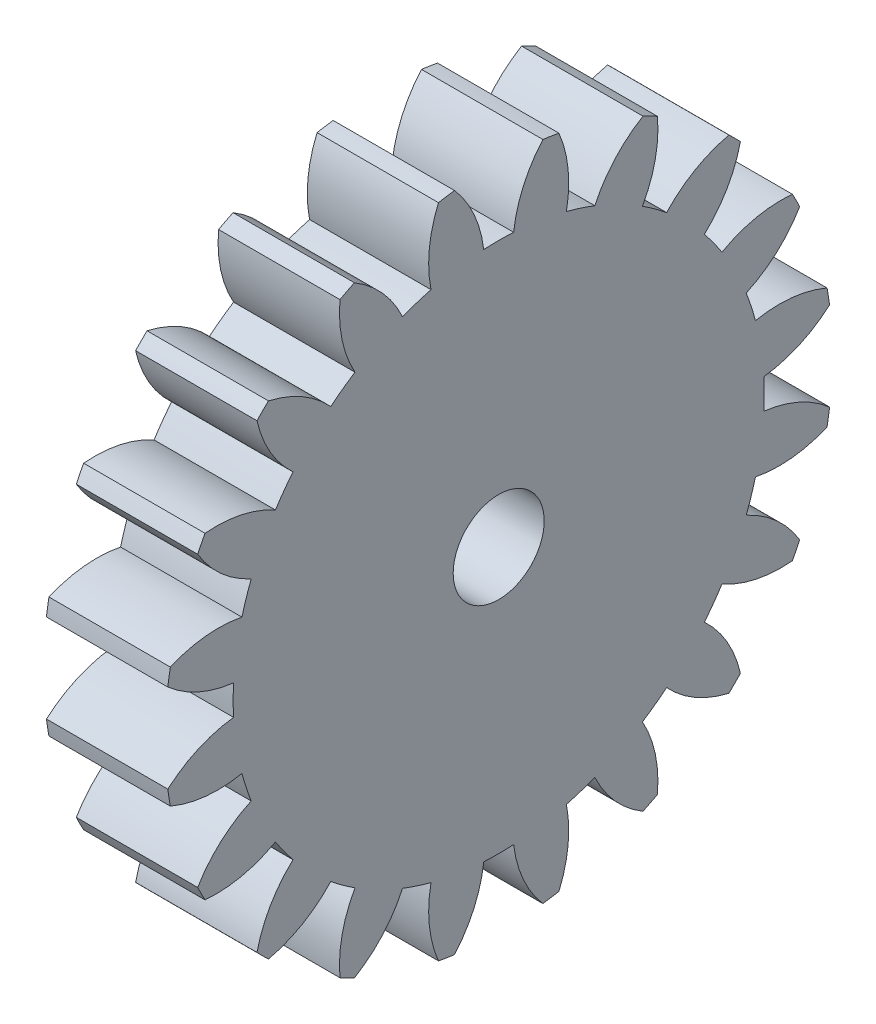
SolidWorks part; units mm, degrees
ref_plane "Plane1" through (0, 0, 0) normal (0, 0, 1) x (1, 0, 0)
ref_plane "Plane2" through (0, 0, 0) normal (0, 1, 0) x (1, 0, 0)
ref_plane "Plane3" through (0, 0, 0) normal (1, 0, 0) x (0, 0, -1)
sketch "HoldingSke" plane through (0, 0, 0) normal (0, 1, 0) x (1, 0, 0)
  line L0 (0, 0) -> (0.1879, -0.0684)
  line L1 (-15, 0) -> (100, 0) construction
  line L2 (0, 0) -> (-2.1039, 2.3779)
  line L3 (0, 0) -> (-11.863, 4.5341)
  line L4 (0, 0) -> (8.1152, 2.9537)
  line L5 (0, 0) -> (-46.8476, -17.4728)
  line L6 (0, 0) -> (-16.5793, -11.1861)
  line L7 (-2.1039, 2.3779) -> (8.6586, 51.2059)
  line L8 (-76.2, 54.61) -> (-73.9, 54.61)
  line L9 (-71.009, 38.7566) -> (-53.1078, 45.2721)
  line L10 (-76.2, 71.12) -> (104.1128, 71.12)
  line L11 (0, 0) -> (-20, 0)
  line L12 (-76.2, 101.6) -> (-76.033, 101.6)
  line L13 (24.9733, 27.94) -> (52.9518, 28.4284)
  line L14 (24.9733, 27.94) -> (24.9743, 27.94)
  line L15 (24.9733, 27.94) -> (100.4006, 29.5858)
  line L16 (-63.627, -5) -> (-12.827, -5)
  circle A0 centre (0, 0) radius 7.5
  circle A1 centre (0, 0) radius 37.5
  circle A2 centre (0, 0) radius 37.5
  circle A3 centre (0, 0) radius 7.5
  dimension "MHD" = 75
  dimension "Hub_dia" = 75
  dimension "Bore" = 15
  dimension "MBD" = 15
  dimension "Num_teeth" = 20
  dimension "Pitch_radius" = 180.3128
  dimension "Pitch" = 0.2
  dimension "Width" = 20
  dimension "Overall_len" = 50
  dimension "Show_teeth" = 20
  dimension "Thickness" = 20
  dimension "OAL" = 50.0001
  dimension "T_dim" = 2.3
  dimension "Ap" = 20
  dimension "H" = 19.05
  dimension "Backlash" = 0.167
  dimension "Addendum_fac" = 1
  dimension "Dedendum_fac" = 1.25
  dimension "Clearance_fac" = 0.25
  dimension "Dedendum_add" = 0.001
  dimension "Module" = 5
sketch "BasProSke" plane through (0, 0, 0) normal (0, 1, 0) x (1, 0, 0)
  line L0 (-10, 0) -> (60, 0) construction
  line L1 (0, 0) -> (0, 55)
  line L2 (0, 0) -> (20, 0)
  line L3 (20, 0) -> (20, 55)
  line L4 (20, 55) -> (0, 55)
  dimension "Diameter" = 110
  dimension "Thickness" = 20
revolve "Base-Revolve" add sketch "BasProSke" angle 360 about L0
sketch "TooCutSke" plane through (0, 0, 0) normal (1, 0, 0) x (0, 0, -1)
  line L1 (0, 0) -> (0, 107) construction
  line L2 (0, 0) -> (-4.2151, 49.822) construction
  line L3 (0, 0) -> (-15.6021, 98.5081) construction
  line L4 (-4.2151, 49.822) -> (-7.8011, 49.254) construction
  arc A0 (2.4648, 43.6795) -> (-2.4648, 43.6795) centre (0, 0) ccw
  arc A1 (7.3009, 54.5389) -> (-7.3009, 54.5389) centre (0, 0) ccw
  circle A2 centre (0, 0) radius 50 construction
  circle A3 centre (0, 0) radius 46.9846 construction
  arc A4 (-2.4648, 43.6795) -> (-7.3009, 54.5389) centre (-22.3276, 41.3405) ccw
  arc A5 (7.3009, 54.5389) -> (2.4648, 43.6795) centre (22.3276, 41.3405) ccw
  dimension "Root_dia" = 87.498
  dimension "Overcut_dia" = 110.0508
  dimension "Pitch_dia" = 100
  dimension "Base_dia" = 93.9693
  dimension "Flank_rad" = 20
  dimension "Half_ang" = 9
  dimension "Half_CT" = 3.6307
extrude "ToothCut" cut sketch "TooCutSke" along normal through all
fillet "Breaks" [suppressed] radius 0.1 tangent propagation no
fillet "RootFillets" [suppressed] radius 1.251
pattern_circular "TeethCuts" count 20 every 18 about axis through (-10, 0, 0) along (1, 0, 0) of "ToothCut", "RootFillets", "Breaks"
sketch "HubNeaOneSke" [suppressed] plane through (0, 0, 0) normal (-1, 0, 0) x (0, 0, 1)
  circle A0 centre (0, 0) radius 12.7
  dimension "Diameter" = 75
extrude "HubNearOne" [suppressed] add sketch "HubNeaOneSke" along normal blind 30.0001
sketch "HubNeaBotSke" [suppressed] plane through (0, 0, 0) normal (-1, 0, 0) x (0, 0, 1)
  circle A0 centre (0, 0) radius 12.7
  dimension "Diameter" = 75
extrude "HubNearBoth" [suppressed] add sketch "HubNeaBotSke" along normal blind 15
ref_plane "FarPln" through (20, 0, 0) normal (1, 0, 0) x (0, 0, -1)
sketch "HubFarSke" [suppressed] plane through (12.7, 0, 0) normal (1, 0, 0) x (0, 0, -1)
  circle A0 centre (0, 0) radius 12.7
  dimension "Diameter" = 75
extrude "HubFar" [suppressed] add sketch "HubFarSke" along normal blind 15
sketch "BorSke" plane through (0, 0, 0) normal (1, 0, 0) x (0, 0, -1)
  circle A0 centre (0, 0) radius 7.5
  dimension "Diameter" = 15
extrude "Bore" cut sketch "BorSke" along normal mid plane 100.0001
sketch "KeySke" [suppressed] plane through (0, 0, 0) normal (1, 0, 0) x (0, 0, -1)
  line L0 (-3.175, 0) -> (-3.175, 12.065)
  line L1 (-3.175, 12.065) -> (3.175, 12.065)
  line L2 (3.175, 12.065) -> (3.175, 0)
  line L3 (0, 0) -> (0, 34) construction
  line L4 (-3.175, 0) -> (3.175, 0)
  dimension "Offset" = 9.8
  dimension "Width" = 5
extrude "Keyway" [suppressed] cut sketch "KeySke" along normal mid plane 100.0001
pattern_circular "Keyway2" [suppressed] count 2 every 90 about axis through (-10, 0, 0) along (1, 0, 0)
ref_axis "Axis1" through (20, 0, 0) along (-1, 0, 0)
equation "' \"Module@HoldingSke\" = 6.35"
equation "' \"Num_teeth@HoldingSke\" = 12"
equation "' \"Ap@HoldingSke\" =  20"
equation "' \"Width@HoldingSke\" = 0.5 * 25.4"
equation "' \"Hub_dia@HoldingSke\"= 1 * 25.4"
equation "' \"Overall_len@HoldingSke\" = 1.0 * 25.4"
equation "' \"Bore@HoldingSke\" = 0.75 * 25.4"
equation "' \"T_dim@HoldingSke\" = 0.1 * 25.4"
equation "' \"Width@KeySke\" = 0.25 * 25.4"
equation "' \"Show_teeth@HoldingSke\" = 13"
equation "' \"Backlash@HoldingSke\" = 0.009 * 25.4"
equation "' \"Addendum_fac@HoldingSke\" = 1.0"
equation "' \"Dedendum_fac@HoldingSke\" = 1.25"
equation "' \"Dedendum_add@HoldingSke\" = 0.00005 * 25.4"
equation "' \"Clearance_fac@HoldingSke\" = 0.25"
equation "\"Pitch@HoldingSke\" = 1 / \"Module@HoldingSke\""
equation "\"Overcut_dia@TooCutSke\" = (\"Num_teeth@HoldingSke\" + 2 * \"Addendum_fac@HoldingSke\") / \"Pitch@HoldingSke\" + 0.002 * 25.4"
equation "\"Pitch_dia@TooCutSke\" = \"Num_teeth@HoldingSke\" / \"Pitch@HoldingSke\""
equation "\"Base_dia@TooCutSke\" = \"Num_teeth@HoldingSke\" / \"Pitch@HoldingSke\" * cos((\"Ap@HoldingSke\"  * 3.14159265 / 180))"
equation "\"Root_dia@TooCutSke\" = (\"Num_teeth@HoldingSke\" + 2) / \"Pitch@HoldingSke\" - 2 * (\"Addendum_fac@HoldingSke\" + \"Dedendum_fac@HoldingSke\") / \"Pitch@HoldingSke\" - \"Dedendum_add@HoldingSke\" * 2"
equation "\"Half_ang@TooCutSke\" = 180 / \"Num_teeth@HoldingSke\""
equation "\"Half_CT@TooCutSke\" = \"Num_teeth@HoldingSke\" / \"Pitch@HoldingSke\" * sin((3.14159265 / 2 / \"Num_teeth@HoldingSke\")) / 2 - 7 * \"Backlash@HoldingSke\" / 4"
equation "\"Flank_rad@TooCutSke\" = \"Num_teeth@HoldingSke\" / \"Pitch@HoldingSke\" / 5"
equation "\"Radius@RootFillets\" = \"Clearance_fac@HoldingSke\" / \"Pitch@HoldingSke\" + \"Dedendum_add@HoldingSke\""
equation "\"Break_rad@Breaks\" = 0.02 / \"Pitch@HoldingSke\""
equation "\"Thickness@HoldingSke\" = \"Width@HoldingSke\""
equation "\"OAL@HoldingSke\" = \"Thickness@HoldingSke\""
equation "\"MHD@HoldingSke\" = (\"Num_teeth@HoldingSke\" + 2) / \"Pitch@HoldingSke\" - 2 * (\"Addendum_fac@HoldingSke\" + \"Dedendum_fac@HoldingSke\")  / \"Pitch@HoldingSke\" - \"Dedendum_add@HoldingSke\" * 2"
equation "\"MBD@HoldingSke\" = (\"Num_teeth@HoldingSke\" + 2) / \"Pitch@HoldingSke\" - 2 * (\"Addendum_fac@HoldingSke\" + \"Dedendum_fac@HoldingSke\")  / \"Pitch@HoldingSke\" - \"Dedendum_add@HoldingSke\" * 2 - 0.002 * 25.4"
equation "\"MHD@HoldingSke\" = ((sgn( \"MHD@HoldingSke\" - \"Hub_dia@HoldingSke\" )-1)*( \"MHD@HoldingSke\" - \"Hub_dia@HoldingSke\" ))/-2+ \"Hub_dia@HoldingSke\""
equation "\"MBD@HoldingSke\" = ((sgn( \"MBD@HoldingSke\" - \"Bore@HoldingSke\" )-1)*( \"MBD@HoldingSke\" - \"Bore@HoldingSke\" ))/-2+ \"Bore@HoldingSke\""
equation "\"OAL@HoldingSke\" = ((sgn( \"OAL@HoldingSke\" - \"Overall_len@HoldingSke\" )+1)*( \"OAL@HoldingSke\" - \"Overall_len@HoldingSke\" ))/2 + \"Overall_len@HoldingSke\" + 0.000002 * 25.4"
equation "\"Num_teeth@TeethCuts\" = int( \"Show_teeth@HoldingSke\" ) + 1"
equation "\"Num_teeth@TeethCuts\" = ((sgn( \"Num_teeth@TeethCuts\" - \"Num_teeth@HoldingSke\" )-1)*( \"Num_teeth@TeethCuts\" - \"Num_teeth@HoldingSke\" ))/-2+ \"Num_teeth@HoldingSke\""
equation "\"Num_teeth@TeethCuts\" = ((sgn( \"Num_teeth@TeethCuts\" - 2.0)+1)*( \"Num_teeth@TeethCuts\" - 2.0))/2 +2.0"
equation "\"Angle@TeethCuts\" = 360.0 / \"Num_teeth@HoldingSke\""
equation "\"Diameter@BasProSke\" = (\"Num_teeth@HoldingSke\" + 2 * \"Addendum_fac@HoldingSke\") / \"Pitch@HoldingSke\""
equation "\"Thickness@BasProSke\"  = \"Thickness@HoldingSke\""
equation "' \"Fillet_rad@BasProSke\" =  \"Thickness@HoldingSke\" * 0.05"
equation "\"MHD@HoldingSke\" = ((sgn( \"MHD@HoldingSke\" - \"Root_dia@TooCutSke\" )-1)*( \"MHD@HoldingSke\" - \"Root_dia@TooCutSke\" ))/-2+ \"Root_dia@TooCutSke\""
equation "\"Diameter@HubNeaOneSke\" = \"MHD@HoldingSke\""
equation "\"Length@HubNearOne\" = \"OAL@HoldingSke\" - \"Thickness@BasProSke\""
equation "\"Diameter@HubNeaBotSke\" = \"MHD@HoldingSke\""
equation "\"Length@HubNearBoth\" = ( \"OAL@HoldingSke\" - \"Thickness@BasProSke\" ) / 2.0"
equation "\"Thickness@FarPln\" = \"Thickness@BasProSke\""
equation "\"Diameter@HubFarSke\" = \"MHD@HoldingSke\""
equation "\"Length@HubFar\" = ( \"OAL@HoldingSke\" - \"Thickness@BasProSke\" ) / 2.0"
equation "\"Diameter@BorSke\" = \"MBD@HoldingSke\""
equation "\"D1@Bore\" = \"OAL@HoldingSke\" * 2.0"
equation "\"D1@Keyway\" = \"OAL@HoldingSke\" * 2.0"
equation "\"Offset@KeySke\" = \"T_dim@HoldingSke\" + \"MBD@HoldingSke\" / 2.0"
